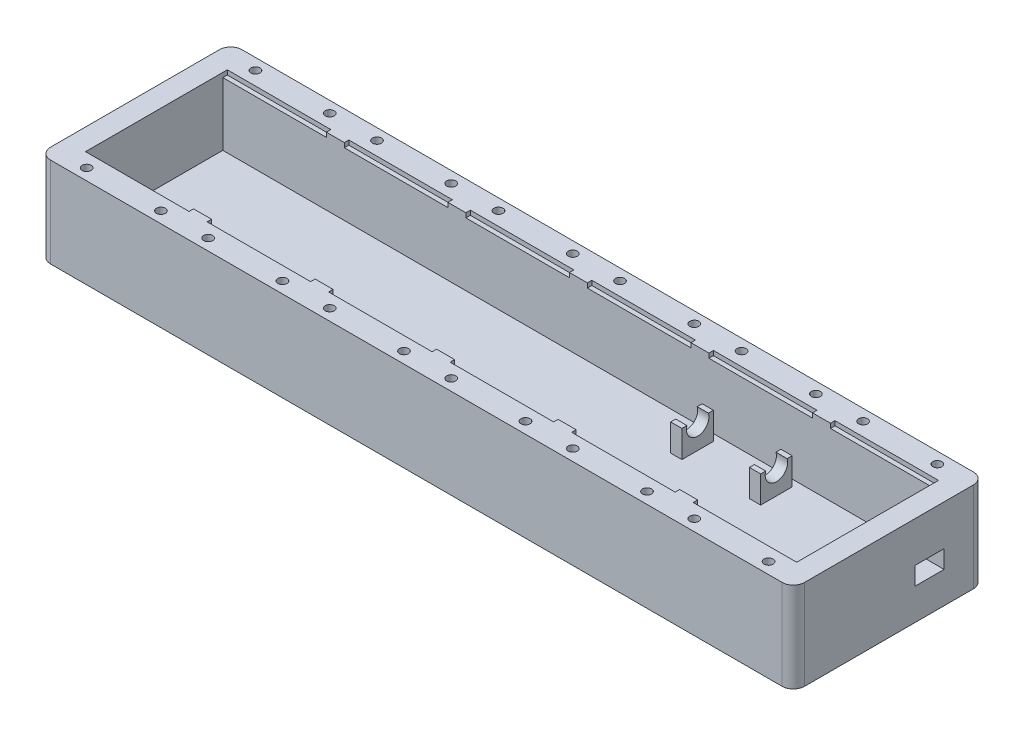
SolidWorks part; units mm, degrees
material "Starkstromplatine"
ref_plane "Ebene vorne" through (0, 0, 0) normal (0, 0, 1) x (1, 0, 0)
ref_plane "Ebene oben" through (0, 0, 0) normal (0, 1, 0) x (1, 0, 0)
ref_plane "Ebene rechts" through (0, 0, 0) normal (1, 0, 0) x (0, 0, -1)
sketch "Skizze2" plane through (0, 0, 0) normal (0, 0, 1) x (1, 0, 0)
  line L1 (0, 0) -> (335, 0)
  line L2 (0, 0) -> (0, 40)
  line L3 (0, 40) -> (335, 40)
  line L4 (335, 0) -> (335, 40)
  dimension "D1" = 335
  dimension "D2" = 40
extrude "Aufsatz-Linear austragen1" add sketch "Skizze2" along normal blind 85
sketch "Skizze4" plane through (0, 40, 0) normal (0, 1, 0) x (1, 0, 0)
  line L1 (9.5, -13) -> (325.5, -13)
  line L2 (9.5, -13) -> (9.5, -72)
  line L3 (9.5, -72) -> (325.5, -72)
  line L4 (325.5, -13) -> (325.5, -72)
  line L6 (0, -85) -> (0, 0) construction
  line L7 (335, -85) -> (335, 0) construction
  line L8 (335, -85) -> (0, -85) construction
  dimension "D1" = 59
  dimension "D2" = 13
  dimension "D3" = 9.5
  dimension "D4" = 9.5
extrude "Schnitt-Linear austragen1" cut sketch "Skizze4" against normal blind 30
sketch "Skizze11" plane through (0, 40, 0) normal (0, 1, 0) x (1, 0, 0)
  line L0 (9.5, -72) -> (325.5, -72) construction
  line L1 (9.5, -13) -> (55.5, -13)
  line L2 (9.5, -13) -> (9.5, -11)
  line L3 (9.5, -11) -> (55.5, -11)
  line L4 (55.5, -13) -> (55.5, -11)
  line L5 (55.5, -72) -> (9.5, -72)
  line L6 (55.5, -72) -> (55.5, -74)
  line L7 (55.5, -74) -> (9.5, -74)
  line L8 (9.5, -72) -> (9.5, -74)
  line L9 (325.5, -13) -> (9.5, -13) construction
  line L10 (63.5, -74) -> (109.5, -74)
  line L11 (63.5, -74) -> (63.5, -72)
  line L12 (63.5, -72) -> (109.5, -72)
  line L13 (109.5, -74) -> (109.5, -72)
  line L14 (117.5, -74) -> (163.5, -74)
  line L15 (117.5, -74) -> (117.5, -72)
  line L16 (117.5, -72) -> (163.5, -72)
  line L17 (163.5, -74) -> (163.5, -72)
  line L18 (171.5, -74) -> (217.5, -74)
  line L19 (171.5, -74) -> (171.5, -72)
  line L20 (171.5, -72) -> (217.5, -72)
  line L21 (217.5, -74) -> (217.5, -72)
  line L22 (225.5, -74) -> (271.5, -74)
  line L23 (225.5, -74) -> (225.5, -72)
  line L24 (225.5, -72) -> (271.5, -72)
  line L25 (271.5, -74) -> (271.5, -72)
  line L26 (279.5, -74) -> (325.5, -74)
  line L27 (279.5, -74) -> (279.5, -72)
  line L28 (279.5, -72) -> (325.5, -72)
  line L29 (325.5, -74) -> (325.5, -72)
  line L30 (325.5, -13) -> (279.5, -13)
  line L31 (325.5, -13) -> (325.5, -11)
  line L32 (325.5, -11) -> (279.5, -11)
  line L33 (279.5, -13) -> (279.5, -11)
  line L34 (0, -85) -> (0, 0) construction
  line L35 (271.5, -13) -> (225.5, -13)
  line L36 (271.5, -13) -> (271.5, -11)
  line L37 (271.5, -11) -> (225.5, -11)
  line L38 (225.5, -13) -> (225.5, -11)
  line L39 (217.5, -13) -> (171.5, -13)
  line L40 (217.5, -13) -> (217.5, -11)
  line L41 (217.5, -11) -> (171.5, -11)
  line L42 (171.5, -13) -> (171.5, -11)
  line L43 (163.5, -13) -> (117.5, -13)
  line L44 (163.5, -13) -> (163.5, -11)
  line L45 (163.5, -11) -> (117.5, -11)
  line L46 (117.5, -13) -> (117.5, -11)
  line L47 (109.5, -13) -> (63.5, -13)
  line L48 (109.5, -13) -> (109.5, -11)
  line L49 (109.5, -11) -> (63.5, -11)
  line L50 (63.5, -13) -> (63.5, -11)
  dimension "D1" = 46
  dimension "D2" = 2
  dimension "D3" = 46
  dimension "D4" = 8
  dimension "D5" = 8
  dimension "D6" = 8
  dimension "D7" = 8
  dimension "D8" = 8
  dimension "D9" = 8
  dimension "D10" = 46
  dimension "D11" = 46
  dimension "D12" = 46
  dimension "D13" = 46
  dimension "D14" = 46
  dimension "D15" = 8
  dimension "D16" = 8
  dimension "D17" = 8
  dimension "D18" = 8
  dimension "D19" = 46
  dimension "D20" = 46
  dimension "D21" = 46
  dimension "D22" = 46
  dimension "D23" = 2
  dimension "D24" = 2
  dimension "D25" = 2
  dimension "D26" = 2
  dimension "D27" = 2
  dimension "D28" = 2
  dimension "D29" = 2
  dimension "D30" = 2
  dimension "D31" = 46
  dimension "D32" = 9.5
  dimension "D33" = 9.5
  dimension "D34" = 2
  dimension "D35" = 2
extrude "Schnitt-Linear austragen4" cut sketch "Skizze11" against normal blind 2
sketch "Skizze17" plane through (0, 40, 0) normal (0, 1, 0) x (1, 0, 0)
  line L0 (55.5, -74) -> (55.5, -72) construction
  line L1 (335, 0) -> (0, 0) construction
  line L2 (335, -85) -> (0, -85) construction
  line L3 (9.5, -72) -> (9.5, -74) construction
  line L4 (9.5, -11) -> (9.5, -74) construction
  line L5 (55.5, -13) -> (55.5, -11) construction
  line L6 (63.5, -72) -> (63.5, -74) construction
  line L7 (109.5, -74) -> (109.5, -72) construction
  line L8 (163.5, -74) -> (163.5, -72) construction
  line L9 (109.5, -13) -> (109.5, -11) construction
  line L10 (171.5, -72) -> (171.5, -74) construction
  line L11 (217.5, -74) -> (217.5, -72) construction
  line L12 (325.5, -74) -> (325.5, -11) construction
  line L13 (279.5, -72) -> (279.5, -74) construction
  line L14 (271.5, -74) -> (271.5, -72) construction
  line L15 (225.5, -72) -> (225.5, -74) construction
  line L16 (63.5, -11) -> (63.5, -13) construction
  line L17 (163.5, -13) -> (163.5, -11) construction
  line L18 (117.5, -11) -> (117.5, -13) construction
  line L19 (171.5, -11) -> (171.5, -13) construction
  line L20 (225.5, -11) -> (225.5, -13) construction
  line L21 (271.5, -13) -> (271.5, -11) construction
  line L22 (279.5, -11) -> (279.5, -13) construction
  line L23 (325.5, -13) -> (325.5, -11) construction
  line L24 (117.5, -72) -> (117.5, -74) construction
  circle A0 centre (49, -80) radius 2
  circle A1 centre (16, -80) radius 2
  circle A2 centre (16, -5) radius 2
  circle A3 centre (49, -5) radius 2
  circle A4 centre (70, -5) radius 2
  circle A5 centre (103, -5) radius 2
  circle A6 centre (70, -80) radius 2
  circle A7 centre (103, -80) radius 2
  circle A8 centre (124, -80) radius 2
  circle A9 centre (157, -80) radius 2
  circle A10 centre (178, -80) radius 2
  circle A11 centre (211, -80) radius 2
  circle A12 centre (232, -80) radius 2
  circle A13 centre (265, -80) radius 2
  circle A14 centre (286, -80) radius 2
  circle A15 centre (319, -80) radius 2
  circle A16 centre (319, -5) radius 2
  circle A17 centre (286, -5) radius 2
  circle A18 centre (265, -5) radius 2
  circle A19 centre (232, -5) radius 2
  circle A20 centre (211, -5) radius 2
  circle A21 centre (178, -5) radius 2
  circle A22 centre (157, -5) radius 2
  circle A23 centre (124, -5) radius 2
  dimension "D1" = 4
  dimension "D2" = 4
  dimension "D3" = 4
  dimension "4" = 4
  dimension "D5" = 5
  dimension "D6" = 5
  dimension "D7" = 5
  dimension "D8" = 5
  dimension "D10" = 6.5
  dimension "D11" = 6.5
  dimension "D12" = 6.5
  dimension "D13" = 4
  dimension "D14" = 4
  dimension "D15" = 4
  dimension "D16" = 4
  dimension "D17" = 4
  dimension "D18" = 4
  dimension "D19" = 4
  dimension "D20" = 4
  dimension "D21" = 4
  dimension "D22" = 4
  dimension "D23" = 6.5
  dimension "D25" = 5
  dimension "D26" = 5
  dimension "D27" = 6.5
  dimension "D28" = 5
  dimension "D29" = 6.5
  dimension "D30" = 5
  dimension "D31" = 6.5
  dimension "D32" = 5
  dimension "D33" = 5
  dimension "D34" = 5
  dimension "D35" = 5
  dimension "D36" = 5
  dimension "D37" = 6.5
  dimension "D38" = 6.5
  dimension "D39" = 6.5
  dimension "D40" = 6.5
  dimension "D41" = 5
  dimension "D42" = 6.5
  dimension "D43" = 4
  dimension "D44" = 4
  dimension "D45" = 4
  dimension "D46" = 4
  dimension "D47" = 4
  dimension "D48" = 4
  dimension "D49" = 4
  dimension "D50" = 4
  dimension "D51" = 4
  dimension "D52" = 4
  dimension "D53" = 5
  dimension "D54" = 6.5
  dimension "D55" = 5
  dimension "D56" = 6.5
  dimension "D58" = 6.5
  dimension "D62" = 6.5
  dimension "D63" = 6.5
  dimension "D64" = 6.5
  dimension "D9" = 6.5
  dimension "D24" = 6.5
  dimension "D57" = 6.5
  dimension "D59" = 6.5
  dimension "D60" = 6.5
  dimension "D61" = 6.5
extrude "Schnitt-Linear austragen6" cut sketch "Skizze17" against normal blind 4
fillet "Verrundung2" radius 5 1 edges at (0, 20, 85)
fillet "Verrundung3" radius 5 1 edges at (0, 20, 0)
fillet "Verrundung4" radius 5 1 edges at (335, 20, 0)
fillet "Verrundung6" radius 5 1 edges at (335, 20, 85)
sketch "Skizze18" plane through (325.5, 0, 0) normal (-1, 0, 0) x (0, 0, 1)
  line L1 (18, 22) -> (31, 22)
  line L2 (18, 22) -> (18, 14)
  line L3 (18, 14) -> (31, 14)
  line L4 (31, 22) -> (31, 14)
  line L5 (72, 10) -> (13, 10) construction
  line L6 (13, 10) -> (13, 38) construction
  dimension "D1" = 5
  dimension "D2" = 13
  dimension "D3" = 8
  dimension "D4" = 4
  dimension "D5" = 4
extrude "Schnitt-Linear austragen7" cut sketch "Skizze18" against normal blind 10
sketch "Skizze20" plane through (0, 10, 0) normal (0, 1, 0) x (1, 0, 0)
  line L0 (325.5, -13) -> (9.5, -13) construction
  line L1 (260.5, -16) -> (265.5, -16)
  line L2 (260.5, -16) -> (260.5, -30)
  line L3 (260.5, -30) -> (265.5, -30)
  line L4 (265.5, -16) -> (265.5, -30)
  line L5 (225.5, -16) -> (230.5, -16)
  line L6 (225.5, -16) -> (225.5, -30)
  line L7 (225.5, -30) -> (230.5, -30)
  line L8 (230.5, -16) -> (230.5, -30)
  line L9 (325.5, -72) -> (325.5, -13) construction
  dimension "D1" = 14
  dimension "D2" = 14
  dimension "D3" = 5
  dimension "D4" = 5
  dimension "D5" = 3
  dimension "D6" = 3
  dimension "D7" = 30
  dimension "D8" = 60
extrude "Aufsatz-Linear austragen2" add sketch "Skizze20" along normal blind 12
sketch "Skizze21" plane through (225.5, 0, 0) normal (-1, 0, 0) x (0, 0, 1)
  line L0 (16, 22) -> (16, 10) construction
  line L1 (16, 22) -> (30, 22) construction
  circle A0 centre (23, 20.5) radius 5
  dimension "D1" = 7
  dimension "D2" = 1.5
extrude "Schnitt-Linear austragen8" cut sketch "Skizze21" against normal blind 71
sketch "Skizze22" plane through (0, 0, 72) normal (0, 0, -1) x (-1, 0, 0)
  line L1 (-325.5, 10) -> (-275.5, 10)
  line L2 (-325.5, 10) -> (-325.5, 17)
  line L3 (-325.5, 17) -> (-275.5, 17)
  line L4 (-275.5, 10) -> (-275.5, 17)
  dimension "D1" = 50
  dimension "D2" = 7
extrude "Aufsatz-Linear austragen3" add sketch "Skizze22" along normal blind 7
